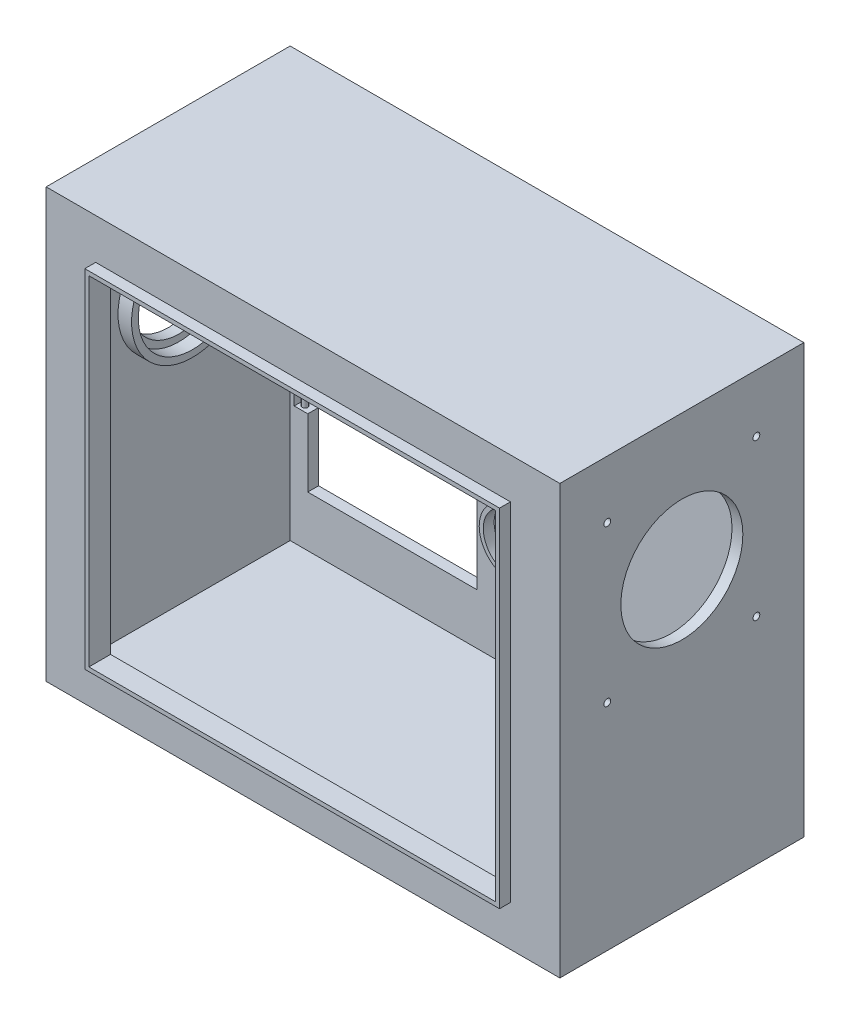
SolidWorks part; units mm, degrees
ref_plane "Alzado" through (0, 0, 0) normal (0, 0, 1) x (1, 0, 0)
ref_plane "Planta" through (0, 0, 0) normal (0, 1, 0) x (1, 0, 0)
ref_plane "Vista lateral" through (0, 0, 0) normal (1, 0, 0) x (0, 0, -1)
sketch "Croquis1" plane through (0, 0, 0) normal (0, 0, 1) x (1, 0, 0)
  line L0 (-189.5, 158) -> (189.5, 158)
  line L1 (-181.5, -150) -> (181.5, -150) construction
  line L2 (-181.5, -150) -> (-181.5, 150) construction
  line L3 (-181.5, 150) -> (181.5, 150) construction
  line L4 (181.5, -150) -> (181.5, 150) construction
  line L5 (-181.5, -150) -> (181.5, 150) construction
  line L6 (-181.5, 150) -> (181.5, -150) construction
  line L7 (189.5, -158) -> (189.5, 158)
  line L8 (-189.5, -158) -> (189.5, -158)
  line L9 (-189.5, -158) -> (-189.5, 158)
  point P0 (0, 0)
  dimension "D1" = 363
  dimension "D2" = 300
  dimension "D3" = 8
extrude "Saliente-Extruir1" add sketch "Croquis1" along normal blind 180
shell "Vaciado1" thickness 8 removed face at (0, 0, 180)
sketch "Croquis2" plane through (-189.5, 0, 0) normal (-1, 0, 0) x (0, 0, 1)
  line L0 (0, 158) -> (90, 158) construction
  line L1 (180, 158) -> (0, 158) construction
  circle A0 centre (90, 58) radius 35
extrude "Cortar-Extruir4" cut sketch "Croquis2" against normal blind 20 contours A0
sketch "Croquis4" plane through (-181.5, 0, 0) normal (1, 0, 0) x (0, 0, -1)
  circle A1 centre (-90, 58) radius 40
  circle A2 centre (-90, 58) radius 45
extrude "Saliente-Extruir4" add sketch "Croquis4" along normal blind 10
sketch "Croquis6" plane through (189.5, 0, 0) normal (1, 0, 0) x (0, 0, -1)
  line L0 (-90, 158) -> (-90, 58) construction
  line L1 (-180, 158) -> (0, 158) construction
  circle A0 centre (-90, 58) radius 45
  dimension "D1" = 90
extrude "Cortar-Extruir6" cut sketch "Croquis6" against normal blind 10 contours A0
sketch "Croquis7" plane through (0, 0, 8) normal (0, 0, 1) x (1, 0, 0)
  circle A3 centre (0, -53) radius 21
  circle A4 centre (0, -53) radius 24
  dimension "D1" = 42
  dimension "D2" = 48
extrude "Saliente-Extruir9" add sketch "Croquis7" along normal blind 18
ref_plane "Plano6" through (0, 0, 180) normal (0, 0, 1) x (1, 0, 0)
sketch "Croquis11" plane through (0, 0, 180) normal (0, 0, 1) x (1, 0, 0)
  line L1 (181.5, 150) -> (-181.5, 150)
  line L2 (181.5, 150) -> (181.5, -150)
  line L3 (181.5, -150) -> (-181.5, -150)
  line L4 (-181.5, 150) -> (-181.5, -150)
  line L5 (181.5, 150) -> (-181.5, -150) construction
  line L6 (181.5, -150) -> (-181.5, 150) construction
  line L7 (-150, 125) -> (150, 125)
  line L8 (-150, 125) -> (-150, -125)
  line L9 (-150, -125) -> (150, -125)
  line L10 (150, 125) -> (150, -125)
  line L11 (-150, 125) -> (150, -125) construction
  line L12 (-150, -125) -> (150, 125) construction
  point P0 (0, 0)
  point P7 (0, 0)
  dimension "D1" = 300
  dimension "D2" = 250
extrude "Saliente-Extruir10" add sketch "Croquis11" against normal blind 8
sketch "Croquis12" plane through (0, 0, 180) normal (0, 0, 1) x (1, 0, 0)
  line L1 (150, -125) -> (-150, -125)
  line L2 (150, -125) -> (150, 125)
  line L3 (150, 125) -> (-150, 125)
  line L4 (-150, -125) -> (-150, 125)
  line L5 (150, -125) -> (-150, 125) construction
  line L6 (150, 125) -> (-150, -125) construction
  line L7 (153, -128) -> (-153, -128)
  line L8 (153, -128) -> (153, 128)
  line L9 (153, 128) -> (-153, 128)
  line L10 (-153, -128) -> (-153, 128)
  line L11 (153, -128) -> (-153, 128) construction
  line L12 (153, 128) -> (-153, -128) construction
  point P0 (0, 0)
  point P8 (0, 0)
  dimension "D1" = 3
  dimension "D2" = 3
extrude "Saliente-Extruir11" add sketch "Croquis12" along normal blind 8
sketch "Croquis20" plane through (0, 0, 8) normal (0, 0, 1) x (1, 0, 0)
  circle A0 centre (0, -53) radius 18.5
  circle A1 centre (0, -53) radius 21
  circle A2 centre (0, -53) radius 21 construction
  dimension "D1" = 37
extrude "Saliente-Extruir19" add sketch "Croquis20" along normal blind 10
hole_wizard "Taladro roscado M63" positions "Croquis3D6" profile "Croquis26" tap size "M6" standard "DIN" end condition through all
sketch3d "Croquis3D6"
  line L2 (-189.5, 0.5, 145) -> (-189.5, 115.5, 145) construction
  line L3 (-189.5, 0.5, 145) -> (-189.5, 0.5, 35) construction
  line L4 (-189.5, 0.5, 35) -> (-189.5, 115.5, 35) construction
  line L5 (-189.5, 115.5, 145) -> (-189.5, 115.5, 35) construction
  line L6 (-189.5, 0.5, 145) -> (-189.5, 115.5, 35) construction
  line L7 (-189.5, 0.5, 35) -> (-189.5, 115.5, 145) construction
  circle A1 centre (-189.5, 58, 90) radius 35 construction
  point P0 (-189.5, 115.5, 35)
  point P2 (-189.5, 115.5, 145)
  point P4 (-189.5, 0.5, 145)
  point P6 (-189.5, 0.5, 35)
  point P265 (-189.5, 58, 90)
  point P268 (-224.5, 58, 90)
  dimension "D1" = 115
  dimension "D2" = 0
  dimension "D3" = 110
sketch "Croquis26" plane through (-189.5, 115.5, 35) normal (0, 1, 0) x (0, 0, 1)
  line L0 (0, 0) -> (0, 379)
  line L1 (0, 379) -> (2.5, 379)
  line L2 (2.5, 379) -> (2.5, 0)
  line L5 (2.5, 0) -> (0, 0)
  line L11 (0, -6.35) -> (0, 107.95) construction
  dimension "Diámetro de perforador para roscar hasta el siguiente" = 5
  dimension "Profundidad de perforador para roscar hasta el siguiente" = 379
cosmetic thread "Rosca de taladro1" parameters "D2"=6
cosmetic thread "Rosca de taladro2" parameters "D2"=6
cosmetic thread "Rosca de taladro3" parameters "D2"=6
cosmetic thread "Rosca de taladro4" parameters "D2"=6
sketch "Croquis27" plane through (0, 0, 0) normal (0, 0, -1) x (-1, 0, 0)
  circle A0 centre (0, -53) radius 11
  circle A1 centre (0, -53) radius 21 construction
  dimension "D1" = 22
sketch "Croquis28" plane through (0, 0, 0) normal (0, 0, -1) x (-1, 0, 0)
  line L0 (0, 0) -> (106, 0) construction
  line L5 (168.5, 112.5) -> (43.5, 112.5)
  line L6 (168.5, 112.5) -> (168.5, -112.5)
  line L11 (168.5, -112.5) -> (43.5, -112.5)
  line L12 (43.5, 112.5) -> (43.5, -112.5)
  line L13 (168.5, 112.5) -> (43.5, -112.5) construction
  line L14 (168.5, -112.5) -> (43.5, 112.5) construction
  point P0 (106, 0)
  dimension "D1" = 125
  dimension "D2" = 225
  dimension "D3" = 106
extrude "Cortar-Extruir7" cut sketch "Croquis28" against normal blind 8 contours L6 L5 L12 L11
sketch "Croquis29" plane through (0, 0, 0) normal (0, 0, -1) x (-1, 0, 0)
  line L1 (168.5, 112.5) -> (168.5, -112.5) construction
  line L2 (168.5, 62.5) -> (178.5, 62.5)
  line L3 (168.5, 62.5) -> (168.5, 42.5)
  line L4 (168.5, 42.5) -> (178.5, 42.5)
  line L5 (178.5, 62.5) -> (178.5, 42.5)
  line L6 (168.5, 62.5) -> (178.5, 42.5) construction
  line L7 (168.5, 42.5) -> (178.5, 62.5) construction
  line L8 (168.5, -42.5) -> (178.5, -42.5)
  line L9 (168.5, -42.5) -> (168.5, -62.5)
  line L10 (168.5, -62.5) -> (178.5, -62.5)
  line L11 (178.5, -42.5) -> (178.5, -62.5)
  line L12 (168.5, -42.5) -> (178.5, -62.5) construction
  line L13 (168.5, -62.5) -> (178.5, -42.5) construction
  point P0 (173.5, -52.5)
  point P2 (173.5, 52.5)
  dimension "D1" = 50
  dimension "D2" = 20
  dimension "D3" = 10
  dimension "D4" = 50
  dimension "D5" = 20
  dimension "D6" = 10
extrude "Cortar-Extruir9" cut sketch "Croquis29" against normal blind 8
sketch "Croquis30" plane through (0, 42.5, 0) normal (0, 1, 0) x (1, 0, 0)
  line L4 (-178.5, -8) -> (-178.5, 0) construction
  line L5 (-168.5, 0) -> (-178.5, 0) construction
  circle A1 centre (-174.5, -4) radius 2
  dimension "D1" = 4
  dimension "D2" = 4
  dimension "D3" = 4
extrude "Saliente-Extruir20" add sketch "Croquis30" along normal blind 9
sketch "Croquis31" plane through (0, -62.5, 0) normal (0, 1, 0) x (1, 0, 0)
  line L0 (-178.5, -8) -> (-178.5, 0) construction
  line L1 (-168.5, 0) -> (-178.5, 0) construction
  circle A0 centre (-174.5, -4) radius 2
  dimension "D3" = 4
  dimension "D1" = 4
  dimension "D2" = 4
extrude "Saliente-Extruir21" add sketch "Croquis31" along normal blind 9
